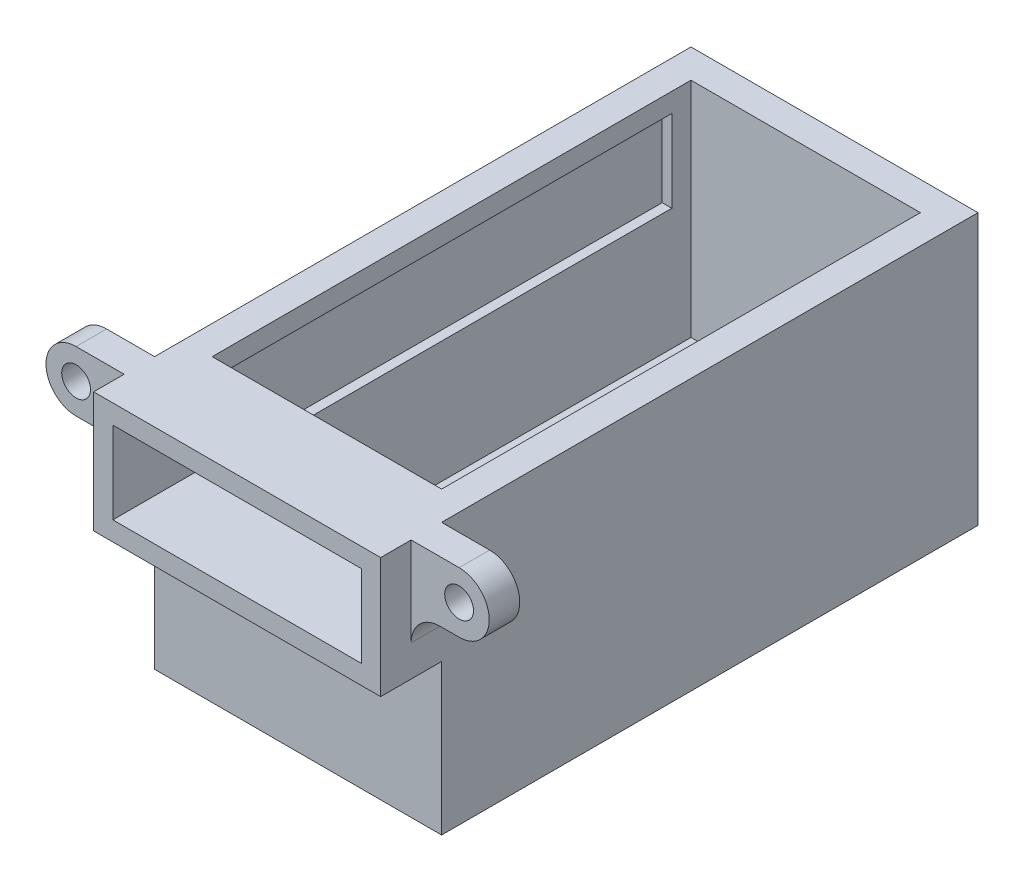
SolidWorks part; units mm, degrees
ref_plane "Front Plane" through (0, 0, 0) normal (0, 0, 1) x (1, 0, 0)
ref_plane "Top Plane" through (0, 0, 0) normal (0, 1, 0) x (1, 0, 0)
ref_plane "Right Plane" through (0, 0, 0) normal (1, 0, 0) x (0, 0, -1)
sketch "Sketch1" plane through (0, 0, 0) normal (0, 0, 1) x (1, 0, 0)
  line L0 (0, 0) -> (0, 12.55)
  line L1 (0, 12.55) -> (29.9, 12.55)
  line L2 (29.9, 12.55) -> (29.9, 0)
  line L3 (29.9, 0) -> (0, 0)
  line L4 (0, 6.275) -> (-5, 6.275)
  line L5 (0, 12.55) -> (-5, 12.55)
  line L6 (29.9, 6.275) -> (34.9, 6.275)
  line L7 (29.9, 12.55) -> (34.9, 12.55)
  arc A0 (-5, 12.55) -> (-5, 6.275) centre (-5, 9.4125) ccw
  arc A1 (34.9, 12.55) -> (34.9, 6.275) centre (34.9, 9.4125) cw
  circle A2 centre (-5, 9.4125) radius 1.5
  circle A3 centre (34.9, 9.4125) radius 1.5
  dimension "D1" = 12.55
  dimension "D5" = 3
  dimension "D6" = 3
  dimension "D2" = 29.9
  dimension "D3" = 5
  dimension "D4" = 5
extrude "Boss-Extrude1" add sketch "Sketch1" along normal blind 3.175 contours L3 L2 L1 L0 | L5 A0 L4 L0 A2 | A1 L7 L2 L6 A3 region at (14.95, 6.275, 0) region at (-2.5, 6.3778, 0) region at (30.0028, 9.4125, 0)
sketch "Sketch2" plane through (0, 0, 3.175) normal (0, 0, 1) x (1, 0, 0)
  line L0 (0, 0) -> (0, 12.55)
  line L1 (-5, 12.55) -> (34.9, 12.55) construction
  line L2 (0, 0) -> (29.9, 0)
  line L3 (29.9, 0) -> (29.9, 12.55)
  line L4 (29.9, 12.55) -> (0, 12.55)
extrude "Boss-Extrude2" add sketch "Sketch2" along normal blind 3.175
sketch "Sketch3" plane through (0, 0, 0) normal (0, 0, -1) x (-1, 0, 0)
  line L0 (-29.9, 0) -> (-29.9, -15.661)
  line L1 (-29.9, -15.661) -> (0, -15.661)
  line L2 (0, -15.661) -> (0, 12.55)
  line L3 (5, 12.55) -> (-34.9, 12.55) construction
  line L4 (0, 12.55) -> (-29.9, 12.55)
  line L5 (-29.9, 12.55) -> (-29.9, 0)
  dimension "D1" = 15.661
extrude "Boss-Extrude3" add sketch "Sketch3" along normal blind 55.88
sketch "Sketch5" plane through (0, 0, 3.175) normal (0, 0, 1) x (1, 0, 0)
  line L0 (29.9, 6.275) -> (34.9, 6.275) construction
  line L1 (29.9, 0) -> (29.9, 12.55) construction
  line L2 (29.9, 6.275) -> (32.9, 6.275)
  line L3 (29.9, 6.275) -> (29.9, 3.275)
  line L4 (29.9, 6.275) -> (0, 6.275) construction
  line L5 (14.95, 6.275) -> (14.95, 12.55) construction
  line L6 (29.9, 12.55) -> (34.9, 12.55) construction
  line L7 (0, 6.275) -> (-3, 6.275)
  line L8 (0, 6.275) -> (0, 3.275)
  circle A0 centre (32.9, 3.275) radius 3
  arc A1 (32.9, 6.275) -> (29.9, 3.275) centre (32.9, 3.275) ccw
  arc A2 (-3, 6.275) -> (0, 3.275) centre (-3, 3.275) cw
  point P10 (14.95, 12.55)
  point P15 (14.95, 12.55)
  point P16 (0, 0)
  line M3 (29.9, 6.275) -> (34.9, 6.275)
  dimension "D1" = 6
extrude "Boss-Extrude4" add sketch "Sketch5" against normal up to surface (3.175 mm away) contours A0 L3 M3 | L7 A2 L8 region at (30.5701, 5.6049, 3.175) up to face at (36.4, 9.4125, 0)
sketch "Sketch6" plane through (0, 0, 6.35) normal (0, 0, 1) x (1, 0, 0)
  line L0 (2, 2) -> (2, 10.55)
  line L1 (2, 10.55) -> (27.9, 10.55)
  line L2 (27.9, 10.55) -> (27.9, 2)
  line L3 (27.9, 2) -> (2, 2)
  line L4 (0, 12.55) -> (0, 0) construction
  line L5 (29.9, 0) -> (29.9, 12.55) construction
  line L6 (0, 0) -> (29.9, 0) construction
  line L7 (29.9, 12.55) -> (0, 12.55) construction
  dimension "D1" = 2
  dimension "D2" = 2
  dimension "D3" = 2
  dimension "D4" = 2
extrude "Cut-Extrude1" cut sketch "Sketch6" against normal offset from surface (57.23 mm away) 5 up to face at (14.95, -1.5555, -55.88)
sketch "Sketch7" plane through (0, 12.55, 0) normal (0, 1, 0) x (1, 0, 0)
  line L0 (26.9, 52.88) -> (3, 52.88)
  line L1 (3, 52.88) -> (3, 3)
  line L2 (3, 3) -> (26.9, 3)
  line L3 (26.9, 3) -> (26.9, 52.88)
  line L4 (0, 55.88) -> (29.9, 55.88) construction
  line L5 (0, 55.88) -> (0, 0) construction
  line L6 (29.9, 55.88) -> (29.9, 0) construction
  line L7 (29.9, 0) -> (34.9, 0) construction
  dimension "D1" = 3
  dimension "D2" = 3
  dimension "D3" = 3
  dimension "D4" = 3
extrude "Cut-Extrude2" cut sketch "Sketch7" against normal offset from surface (23.211 mm away) 5 up to face at (14.95, -15.661, -27.94)
equation "\"wall_thickness\"= 0.125in"
equation "\"base_thickness\"= 0.25in"
equation "\"D1@Boss-Extrude1\"=\"wall_thickness\""
equation "\"D1@Boss-Extrude2\"=\"wall_thickness\""
